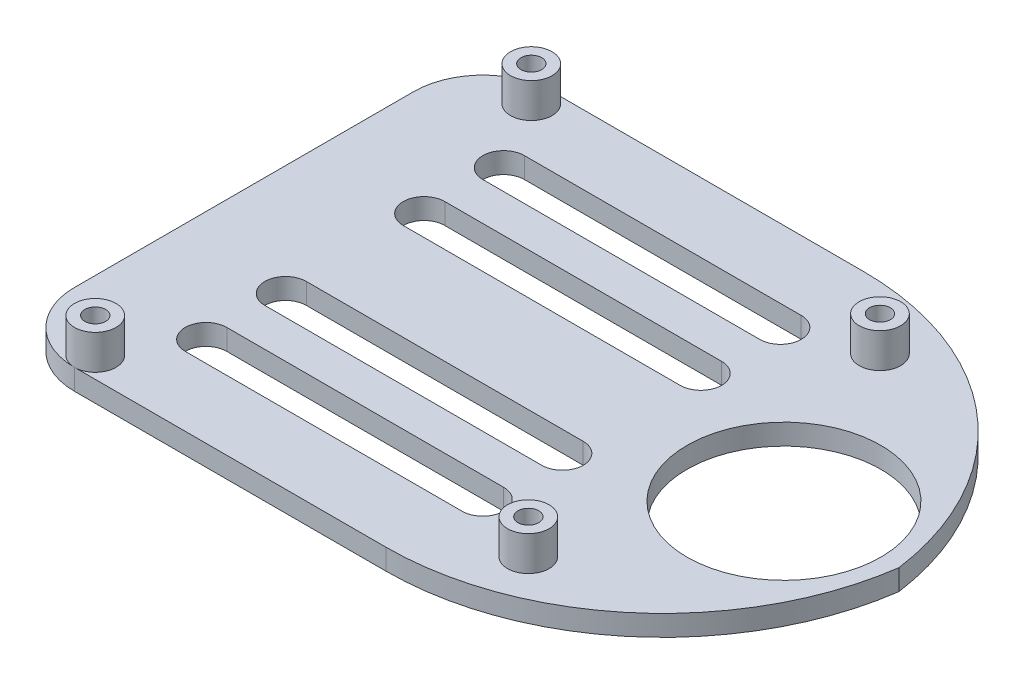
SolidWorks part; units mm, degrees
ref_plane "Plano frontal" through (0, 0, 0) normal (0, 0, 1) x (1, 0, 0)
ref_plane "Plano superior" through (0, 0, 0) normal (0, 1, 0) x (1, 0, 0)
ref_plane "Plano direito" through (0, 0, 0) normal (1, 0, 0) x (0, 0, -1)
sketch "Esboço1" plane through (0, 0, 0) normal (0, 1, 0) x (1, 0, 0)
  line L1 (-47.5, -34.5) -> (47.5, -34.5)
  line L2 (-47.5, -34.5) -> (-47.5, 34.5)
  line L3 (-47.5, 34.5) -> (47.5, 34.5)
  line L4 (47.5, -34.5) -> (47.5, 34.5)
  line L5 (-47.5, -34.5) -> (47.5, 34.5) construction
  line L6 (-47.5, 34.5) -> (47.5, -34.5) construction
  point P0 (0, 0)
  dimension "D1" = 95
  dimension "D2" = 69
extrude "Ressalto-extrusão1" add sketch "Esboço1" along normal blind 3
sketch "Esboço2" plane through (0, 3, 0) normal (0, 1, 0) x (1, 0, 0)
  line L0 (0, 0) -> (47.5, 0) construction
  line L1 (47.5, -34.5) -> (47.5, 34.5) construction
  circle A0 centre (30.5, 0) radius 14
  dimension "D1" = 28
  dimension "D2" = 17
extrude "Corte-extrusão1" cut sketch "Esboço2" against normal through all
sketch "Esboço4" plane through (0, 3, 0) normal (0, 1, 0) x (1, 0, 0)
  line L1 (18.9715, 25.4) -> (18.9715, 34.5) construction
  line L2 (47.5, 0) -> (-47.5, 0) construction
  line L3 (47.5, -34.5) -> (47.5, 34.5) construction
  line L4 (-47.5, 34.5) -> (-47.5, -34.5) construction
  line L5 (-37.5, 31.5) -> (18.9715, 31.5) construction
  line L6 (-37.5, 31.5) -> (18.9715, 25.4) construction
  line L7 (47.5, 34.5) -> (-47.5, 34.5) construction
  circle A0 centre (18.9715, 25.4) radius 3 construction
  circle A3 centre (18.9715, 25.4) radius 1
  circle A4 centre (18.9715, -25.4) radius 1
  circle A5 centre (-37.5, 31.5) radius 1
  circle A6 centre (-37.5, -31.5) radius 1
  circle A7 centre (18.9715, -25.4) radius 3 construction
  circle A9 centre (-37.5, 31.5) radius 3 construction
  dimension "D1" = 50.8
  dimension "D2" = 2
  dimension "D3" = 2
  dimension "D4" = 3
  dimension "D6" = 6
  dimension "D7" = 6
  dimension "D8" = 56.8
  dimension "D9" = 6
  dimension "D5" = 10
extrude "Corte-extrusão2" cut sketch "Esboço4" against normal through all
sketch "Esboço5" plane through (0, 3, 0) normal (0, 1, 0) x (1, 0, 0)
  line L0 (47.5, 0) -> (-47.5, 0) construction
  line L1 (47.5, -34.5) -> (47.5, 34.5) construction
  line L2 (-47.5, 34.5) -> (-47.5, -34.5) construction
  circle A0 centre (-37.5, 31.5) radius 3
  circle A1 centre (-37.5, 31.5) radius 1.5
  circle A2 centre (18.9715, 25.4) radius 1.5
  circle A3 centre (18.9715, 25.4) radius 3
  circle A4 centre (18.9715, -25.4) radius 3
  circle A5 centre (18.9715, -25.4) radius 1.5
  circle A6 centre (-37.5, -31.5) radius 3
  circle A7 centre (-37.5, -31.5) radius 1.5
  dimension "D1" = 6
  dimension "D2" = 3
  dimension "D3" = 3
  dimension "D4" = 6
extrude "Ressalto-extrusão2" add sketch "Esboço5" along normal blind 5
fillet "Filete1" radius 40 2 edges at (47.5, 1.5, -34.5) (47.5, 1.5, 34.5)
fillet "Filete2" radius 10 2 edges at (-47.5, 1.5, 34.5) (-47.5, 1.5, -34.5)
sketch "Esboço7" plane through (0, 3, 0) normal (0, 1, 0) x (1, 0, 0)
  line L0 (16.5, 0) -> (-47.5, 0) construction
  line L1 (-47.5, 24.5) -> (-47.5, -24.5) construction
  line L2 (-31.5, 21.5) -> (8.5, 21.5) construction
  line L5 (-31.5, 10) -> (8.5, 10) construction
  line L6 (-31.5, 13) -> (8.5, 13)
  line L7 (-31.5, 7) -> (8.5, 7)
  line L8 (-31.5, 24.5) -> (8.5, 24.5)
  line L9 (-31.5, 18.5) -> (8.5, 18.5)
  line L10 (7.5, 34.5) -> (-37.5, 34.5) construction
  line L11 (-31.5, -21.5) -> (8.5, -21.5) construction
  line L12 (-31.5, -24.5) -> (8.5, -24.5)
  line L13 (-31.5, -18.5) -> (8.5, -18.5)
  line L14 (-31.5, -10) -> (8.5, -10) construction
  line L15 (-31.5, -13) -> (8.5, -13)
  line L16 (-31.5, -7) -> (8.5, -7)
  circle A0 centre (30.5, 0) radius 14 construction
  arc A3 (-31.5, 13) -> (-31.5, 7) centre (-31.5, 10) ccw
  arc A4 (8.5, 7) -> (8.5, 13) centre (8.5, 10) ccw
  arc A5 (-31.5, 24.5) -> (-31.5, 18.5) centre (-31.5, 21.5) ccw
  arc A6 (8.5, 18.5) -> (8.5, 24.5) centre (8.5, 21.5) ccw
  arc A7 (-31.5, -24.5) -> (-31.5, -18.5) centre (-31.5, -21.5) cw
  arc A8 (8.5, -18.5) -> (8.5, -24.5) centre (8.5, -21.5) cw
  arc A9 (-31.5, -13) -> (-31.5, -7) centre (-31.5, -10) cw
  arc A10 (8.5, -7) -> (8.5, -13) centre (8.5, -10) cw
  point P8 (-11.5, 21.5)
  point P15 (-11.5, 10)
  point P24 (-11.5, -21.5)
  point P31 (-11.5, -10)
  dimension "D5" = 16
  dimension "D1" = 10
  dimension "D2" = 3
  dimension "D3" = 40
  dimension "D4" = 7
  dimension "D6" = 16
extrude "Corte-extrusão3" cut sketch "Esboço7" against normal through all
